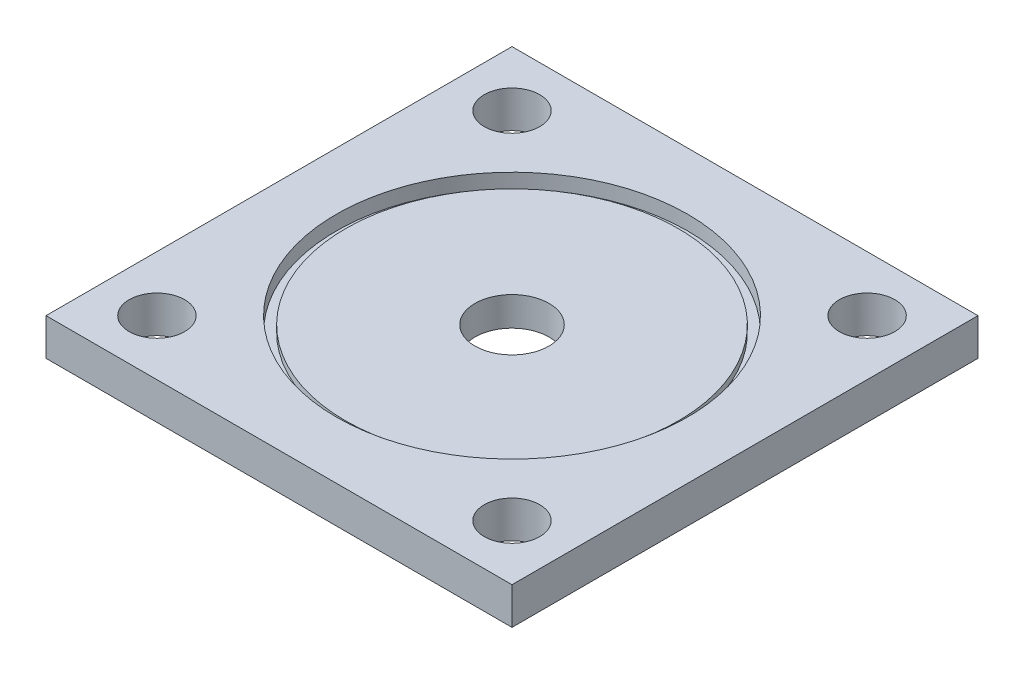
SolidWorks part; units mm, degrees
ref_plane "Front Plane" through (0, 0, 0) normal (0, 0, 1) x (1, 0, 0)
ref_plane "Top Plane" through (0, 0, 0) normal (0, 1, 0) x (1, 0, 0)
ref_plane "Right Plane" through (0, 0, 0) normal (1, 0, 0) x (0, 0, -1)
sketch "plateOutline" plane through (0, 0, 0) normal (0, 1, 0) x (1, 0, 0)
  line L1 (-40, -40) -> (40, -40)
  line L2 (-40, -40) -> (-40, 40)
  line L3 (-40, 40) -> (40, 40)
  line L4 (40, -40) -> (40, 40)
  line L5 (-40, -40) -> (40, 40) construction
  line L6 (-40, 40) -> (40, -40) construction
  line L7 (-40, -40) -> (40, -40) construction
  line L8 (-40, -40) -> (-40, 40) construction
  line L9 (-40, 40) -> (40, 40) construction
  line L10 (40, -40) -> (40, 40) construction
  point P0 (0, 0)
  dimension "D1" = 80
sketch "railGuides" plane through (0, 0, 0) normal (0, 1, 0) x (1, 0, 0)
  line L0 (-30.48, 30.48) -> (30.48, 30.48) construction
  line L1 (30.48, -30.48) -> (30.48, 30.48) construction
  line L2 (-30.48, -30.48) -> (30.48, -30.48) construction
  line L3 (-30.48, -30.48) -> (-30.48, 30.48) construction
  line L5 (-40.005, -40.005) -> (40.005, -40.005) construction
  line L11 (-40.005, -40.005) -> (-40.005, 40.005) construction
  line L12 (-40.005, 40.005) -> (40.005, 40.005) construction
  line L13 (40.005, -40.005) -> (40.005, 40.005) construction
  line L14 (-40.005, -40.005) -> (40.005, 40.005) construction
  line L15 (-40.005, 40.005) -> (40.005, -40.005) construction
  circle A0 centre (-30.48, 30.48) radius 4.7625
  circle A1 centre (30.48, 30.48) radius 4.7625
  circle A2 centre (30.48, -30.48) radius 4.7625
  circle A3 centre (-30.48, -30.48) radius 4.7625
  point P1 (0, 0)
  dimension "D1" = 80.01
  dimension "D3" = 9.525
  dimension "D4" = 9.525
  dimension "D5" = 9.525
  dimension "D6" = 9.525
  dimension "D7" = 9.525
  dimension "D2" = 80.01
sketch "FuelGrainMounting" plane through (0, 0, 0) normal (0, 1, 0) x (1, 0, 0)
  circle A0 centre (0, 0) radius 30.1625
sketch "GasIntake" plane through (0, 0, 0) normal (0, 1, 0) x (1, 0, 0)
  line L0 (-40, 40) -> (40, -40) construction
  circle A0 centre (0, 0) radius 6.35
extrude "Boss-Extrude1" add sketch "plateOutline" along normal blind 6.35 contours L3 L4 L1 L2
extrude "Cut-Extrude1" cut sketch "railGuides" along normal blind 10 contours A0 | A3 | A1 | A2 region at (-30.48, 0, -30.48)
extrude "Cut-Extrude2" cut sketch "FuelGrainMounting" along normal blind 5 from offset 5
extrude "Cut-Extrude3" cut sketch "GasIntake" along normal blind 5
sketch "Sketch1" plane through (0, 0, 0) normal (0, 1, 0) x (1, 0, 0)
  circle A0 centre (0, 0) radius 28.575
  circle A2 centre (0, 0) radius 30.1625
  dimension "D1" = 60.325
  dimension "D2" = 57.15
extrude "Cut-Extrude4" cut sketch "Sketch1" against normal blind 1.143 from offset 5
